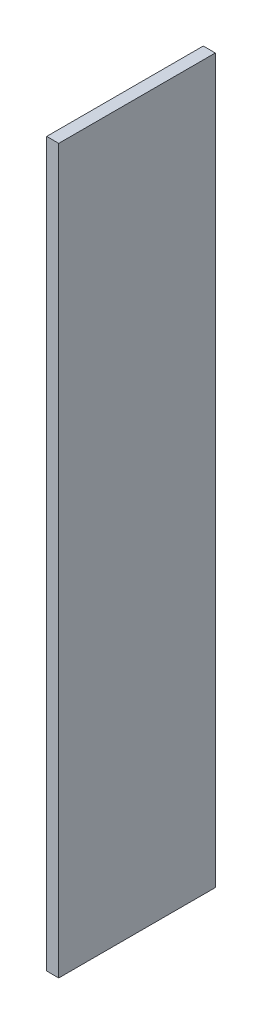
SolidWorks part; units mm, degrees
ref_plane "Plan de face" through (0, 0, 0) normal (0, 0, 1) x (1, 0, 0)
ref_plane "Plan de dessus" through (0, 0, 0) normal (0, 1, 0) x (1, 0, 0)
ref_plane "Plan de droite" through (0, 0, 0) normal (1, 0, 0) x (0, 0, -1)
sketch "Esquisse1" plane through (0, 0, 0) normal (0, 0, 1) x (1, 0, 0)
  line L0 (-112.7306, 0) -> (-222.1354, 0) construction
  line L1 (-155.642, 600) -> (-165.642, 600)
  line L2 (-155.642, 600) -> (-155.642, 0)
  line L3 (-155.642, 0) -> (-165.642, 0)
  line L4 (-165.642, 600) -> (-165.642, 0)
  dimension "D1" = 10
extrude "Boss.-Extru.1" add sketch "Esquisse1" along normal up to surface (129.974 mm away)
